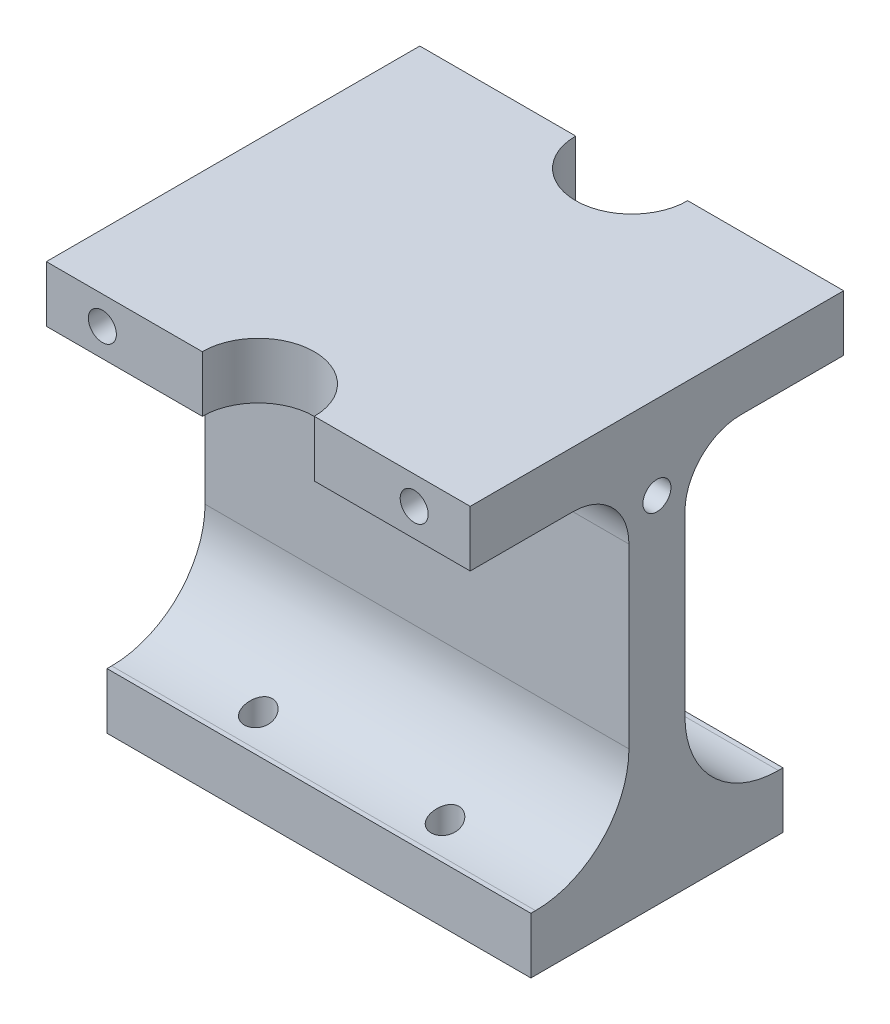
SolidWorks part; units mm, degrees
ref_plane "Płaszczyzna przednia" through (0, 0, 0) normal (0, 0, 1) x (1, 0, 0)
ref_plane "Płaszczyzna górna" through (0, 0, 0) normal (0, 1, 0) x (1, 0, 0)
ref_plane "Płaszczyzna prawa" through (0, 0, 0) normal (1, 0, 0) x (0, 0, -1)
sketch "Sketch1" plane through (0, 0, 0) normal (0, 1, 0) x (1, 0, 0)
  line L1 (0, 0) -> (45.4, 0)
  line L2 (0, 0) -> (0, 27)
  line L3 (0, 27) -> (45.4, 27)
  line L4 (45.4, 0) -> (45.4, 27)
  dimension "D1" = 45.4
  dimension "D2" = 27
extrude "Boss-Extrude1" add sketch "Sketch1" along normal blind 6
sketch "Sketch4" plane through (0, 6, 0) normal (0, 1, 0) x (1, 0, 0)
  line L0 (0, 27) -> (0, 0) construction
  line L1 (0, 16.5) -> (45.4, 16.5)
  line L2 (0, 16.5) -> (0, 10.5)
  line L3 (0, 10.5) -> (45.4, 10.5)
  line L4 (45.4, 16.5) -> (45.4, 10.5)
  line L5 (45.4, 0) -> (45.4, 27) construction
  line L6 (0, 0) -> (45.4, 0) construction
  dimension "D1" = 6
  dimension "D2" = 10.5
extrude "Boss-Extrude2" add sketch "Sketch4" along normal blind 35
fillet "Fillet3" radius 10 2 edges at (22.7, 6, -10.5) (22.7, 6, -16.5)
ref_plane "Plane3" through (0, 16, 0) normal (0, -1, 0) x (-1, 0, 0)
hole_wizard "Ø3.0mm Dowel Hole1" positions "Sketch2" profile "Sketch3" hole size "Ø3.0" standard "ANSI Metric" end condition up to next
sketch "Sketch2" plane through (0, 16, 0) normal (0, 1, 0) x (1, 0, 0)
  point P0 (12.7, 23.5)
  point P2 (32.7, 23.5)
  point P4 (32.7, 3.5)
  point P6 (12.7, 3.5)
  dimension "D1" = 20
  dimension "D2" = 20
  dimension "D3" = 20
sketch "Sketch3" plane through (12.7, 16, -23.5) normal (1, 0, 0) x (0, 0, 1)
  line L0 (0, 0) -> (0, 16)
  line L1 (0, 16) -> (1.5, 16)
  line L2 (1.5, 16) -> (1.5, 0)
  line L5 (1.5, 0) -> (0, 0)
  line L11 (0, -6.35) -> (0, 107.95) construction
  dimension "Thru Hole Dia." = 3
  dimension "Thru Hole Depth" = 16
sketch "Sketch5" plane through (0, 41, 0) normal (0, 1, 0) x (1, 0, 0)
  line L0 (45.4, 13.5) -> (0, 13.5) construction
  line L1 (45.4, 33.5) -> (28.7, 33.5)
  line L2 (45.4, 33.5) -> (45.4, -6.5)
  line L3 (45.4, -6.5) -> (28.7, -6.5)
  line L4 (0, 33.5) -> (0, -6.5)
  line L5 (45.4, 33.5) -> (0, -6.5) construction
  line L6 (45.4, -6.5) -> (0, 33.5) construction
  line L7 (45.4, 10.5) -> (45.4, 16.5) construction
  line L8 (0, 16.5) -> (0, 10.5) construction
  line L9 (16.7, 33.5) -> (0, 33.5)
  line L10 (16.7, -6.5) -> (0, -6.5)
  line L11 (22.7, 33.5) -> (22.7, -6.5) construction
  line L12 (45.4, 33.5) -> (0, 33.5) construction
  line L13 (15.0168, -6.5) -> (31.9525, -6.5) construction
  arc A0 (16.7, 33.5) -> (28.7, 33.5) centre (22.7, 33.5) ccw
  arc A1 (28.7, -6.5) -> (16.7, -6.5) centre (22.7, -6.5) ccw
  point P4 (22.7, 13.5)
  dimension "D2" = 6
  dimension "D3" = 6
  dimension "D4" = 22.7
  dimension "D1" = 40
extrude "Boss-Extrude3" add sketch "Sketch5" along normal blind 6
fillet "Fillet4" radius 6 2 edges at (22.7, 41, -10.5) (22.7, 41, -16.5)
hole_wizard "Ø3.0 (3) Diameter Hole1" positions "Sketch6" profile "Sketch7" hole size "Ø3.0" standard "ANSI Metric"
sketch "Sketch6" plane through (0, 0, 6.5) normal (0, 0, 1) x (1, 0, 0)
  line L0 (0, 47) -> (0, 41) construction
  line L1 (0, 41) -> (16.7, 41) construction
  line L2 (45.4, 47) -> (45.4, 41) construction
  point P0 (6, 44)
  point P2 (39.4, 44)
  dimension "D1" = 6
  dimension "D2" = 3
  dimension "D3" = 6
sketch "Sketch7" plane through (6, 44, 6.5) normal (1, 0, 0) x (0, -1, 0)
  line L0 (0, 0) -> (0, 6.9013)
  line L1 (0, 6.9013) -> (1.5, 6)
  line L2 (1.5, 6) -> (1.5, 0)
  line L5 (1.5, 0) -> (0, 0)
  line L10 (0, 6.9013) -> (-1.5, 6) construction
  line L11 (0, -6.35) -> (0, 107.95) construction
  dimension "Hole Dia." = 3
  dimension "Hole Depth" = 6
  dimension "Drill Angle" = 118
hole_wizard "Ø3.0 (3) Diameter Hole2" positions "Sketch8" profile "Sketch9" hole size "Ø3.0" standard "ANSI Metric"
sketch "Sketch8" plane through (0, 0, -33.5) normal (0, 0, -1) x (-1, 0, 0)
  line L0 (-45.4, 47) -> (-28.7, 47) construction
  line L2 (-45.4, 47) -> (-45.4, 41) construction
  line L3 (0, 47) -> (0, 41) construction
  point P0 (-39.4, 44)
  point P2 (-6, 44)
  dimension "D1" = 3
  dimension "D2" = 6
  dimension "D3" = 6
sketch "Sketch9" plane through (39.4, 44, -33.5) normal (1, 0, 0) x (0, 1, 0)
  line L0 (0, 0) -> (0, 6.9013)
  line L1 (0, 6.9013) -> (1.5, 6)
  line L2 (1.5, 6) -> (1.5, 0)
  line L5 (1.5, 0) -> (0, 0)
  line L10 (0, 6.9013) -> (-1.5, 6) construction
  line L11 (0, -6.35) -> (0, 107.95) construction
  dimension "Hole Dia." = 3
  dimension "Hole Depth" = 6
  dimension "Drill Angle" = 118
hole_wizard "Ø3.0 (3) Diameter Hole3" positions "Sketch10" profile "Sketch12" hole size "Ø3.0" standard "ANSI Metric"
sketch "Sketch10" plane through (45.4, 0, 0) normal (1, 0, 0) x (0, 0, -1)
  point P0 (13.5, 38)
sketch "Sketch12" plane through (45.4, 38, -13.5) normal (0, 1, 0) x (0, 0, -1)
  line L0 (0, 0) -> (0, 12.9013)
  line L1 (0, 12.9013) -> (1.5, 12)
  line L2 (1.5, 12) -> (1.5, 0)
  line L5 (1.5, 0) -> (0, 0)
  line L10 (0, 12.9013) -> (-1.5, 12) construction
  line L11 (0, -6.35) -> (0, 107.95) construction
  dimension "Hole Dia." = 3
  dimension "Hole Depth" = 12
  dimension "Drill Angle" = 118
ref_plane "Plane4" through (22.7, 0, 0) normal (-1, 0, 0) x (0, 0, 1)
mirror "Mirror1" about plane through (22.7, 0, 0) normal (-1, 0, 0) of "Ø3.0 (3) Diameter Hole3"
